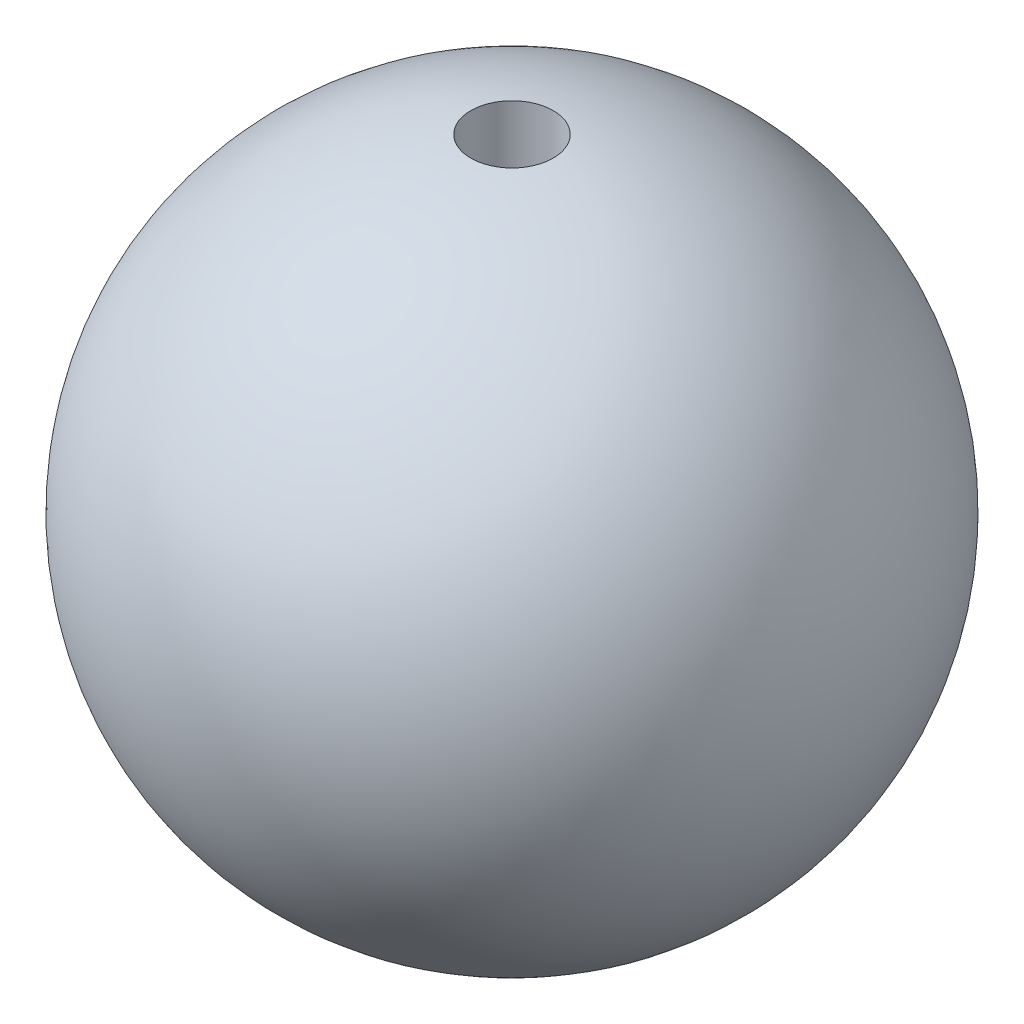
SolidWorks part; units mm, degrees
material "Pine"
ref_plane "Front Plane" through (0, 0, 0) normal (0, 0, 1) x (1, 0, 0)
ref_plane "Top Plane" through (0, 0, 0) normal (0, 1, 0) x (1, 0, 0)
ref_plane "Right Plane" through (0, 0, 0) normal (1, 0, 0) x (0, 0, -1)
sketch "Sketch1" plane through (0, 0, 0) normal (0, 0, 1) x (1, 0, 0)
  line L0 (0, 0) -> (0, 44.45)
  dimension "D1" = 44.45
sketch "Sketch2" plane through (0, 0, 0) normal (0, 0, 1) x (1, 0, 0)
  line L0 (0, 12.7) -> (0, -12.7)
  arc A0 (0, -12.7) -> (0, 12.7) centre (0, 0) ccw
ref_axis "Axis1" through (0, 44.45, 0) along (0, -1, 0)
revolve "Revolve1" add sketch "Sketch2" angle 360 about L0
sketch "Sketch3" plane through (0, 0, 0) normal (0, 1, 0) x (1, 0, 0)
  circle A0 centre (0, 0) radius 1.5875
  dimension "D1" = 3.175
extrude "Cut-Extrude1" cut sketch "Sketch3" along normal through all
